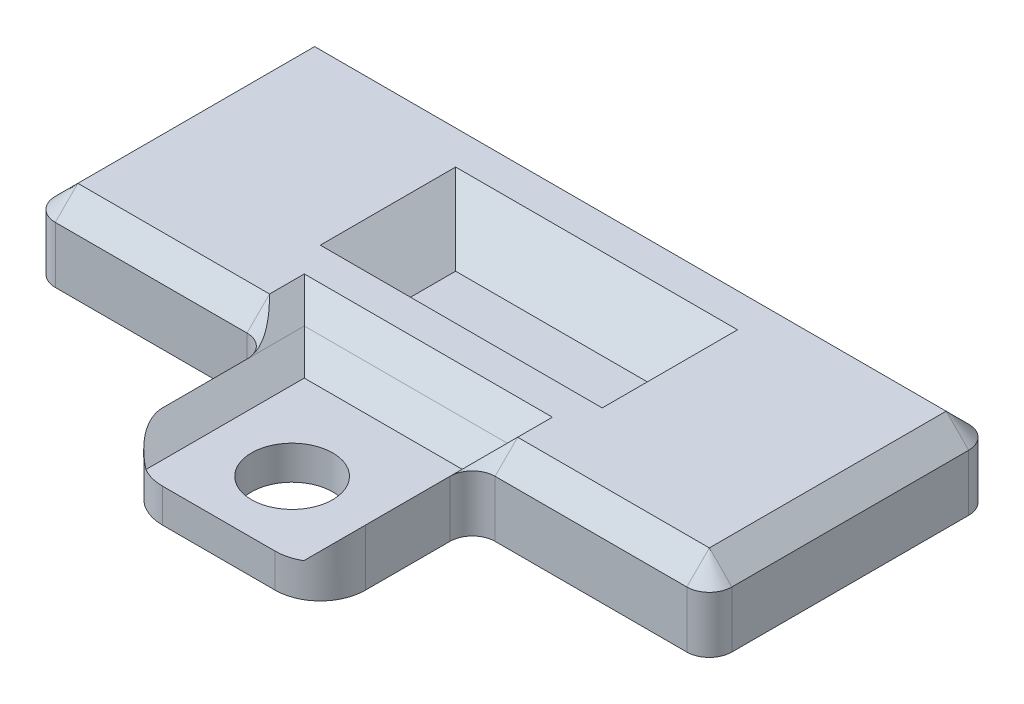
SolidWorks part; units mm, degrees
ref_plane "Front Plane" through (0, 0, 0) normal (0, 0, 1) x (1, 0, 0)
ref_plane "Top Plane" through (0, 0, 0) normal (0, 1, 0) x (1, 0, 0)
ref_plane "Right Plane" through (0, 0, 0) normal (1, 0, 0) x (0, 0, -1)
sketch "Sketch1" plane through (0, 0, 0) normal (0, 1, 0) x (1, 0, 0)
  line L0 (-4.5, -6.25) -> (-15, -6.25)
  line L1 (15, -6.25) -> (4.5, -6.25)
  line L2 (15, -6.25) -> (15, 6.25)
  line L3 (15, 6.25) -> (-15, 6.25)
  line L4 (-15, -6.25) -> (-15, 6.25)
  line L5 (15, -6.25) -> (-15, 6.25) construction
  line L6 (15, 6.25) -> (-15, -6.25) construction
  line L8 (-4.5, -6.25) -> (-4.5, -13)
  line L9 (-4.5, -13) -> (4.5, -13)
  line L10 (4.5, -6.25) -> (4.5, -13)
  line L11 (0, -6.25) -> (4.5, -13) construction
  line L12 (-4.5, -13) -> (0, -6.25) construction
  point P0 (0, 0)
  point P6 (0, -6.25)
  dimension "D1" = 30
  dimension "D2" = 12.5
  dimension "D3" = 6.75
  dimension "D4" = 9
  dimension "D5" = 10.5
extrude "Boss-Extrude1" add sketch "Sketch1" along normal blind 3.5
sketch "Sketch2" plane through (0, 0, 0) normal (0, -1, 0) x (1, 0, 0)
  line L0 (15, -6.25) -> (-15, -6.25) construction
  line L1 (-13, -5) -> (-9, -5)
  line L2 (-13, -5) -> (-13, 5)
  line L3 (-13, 5) -> (-9, 5)
  line L4 (-9, -5) -> (-9, 5)
  line L5 (-13, -5) -> (-9, 5) construction
  line L6 (-13, 5) -> (-9, -5) construction
  point P0 (-11, 0)
  dimension "D1" = 11
  dimension "D2" = 10
  dimension "D3" = 4
  dimension "D4" = 1.25
extrude "Cut-Extrude1" cut sketch "Sketch2" against normal blind 2.5
fillet "Fillet1" radius 1 6 edges at (15, 1.75, -6.25) (15, 1.75, 6.25) (4.5, 1.75, 6.25) (-4.5, 1.75, 6.25) (-15, 1.75, 6.25) (-15, 1.75, -6.25)
fillet "Fillet2" radius 1 4 edges at (-13, 1.25, 5) (-9, 1.25, 5) (-13, 1.25, -5) (-9, 1.25, -5)
mirror "Mirror1" about plane through (0, 0, 0) normal (1, 0, 0) of "Cut-Extrude1", "Fillet2"
sketch "Sketch3" plane through (0, 3.5, 0) normal (0, 1, 0) x (1, 0, 0)
  line L4 (-4.5, -13) -> (4.5, -13)
  line L5 (-4.5, -13) -> (-4.5, -4.7098)
  line L6 (-4.5, -4.7098) -> (4.5, -4.7098)
  line L7 (4.5, -13) -> (4.5, -4.7098)
  point P5 (-4.5, -7.25)
extrude "Cut-Extrude3" cut sketch "Sketch3" against normal blind 2
chamfer "Chamfer2" distance 1 angle 45 3 edges at (4.5, 1.5, 5.9799) (0, 1.5, 4.7098) (-4.5, 1.5, 5.9799)
chamfer "Chamfer3" distance 1 angle 45 14 edges at (-4.7929, 3.5, 6.5429) (-9.75, 3.5, 6.25) (-14.7071, 3.5, 5.9571) (-15, 3.5, 0) (-14.7071, 3.5, -5.9571) (0, 3.5, -6.25) (14.7071, 3.5, -5.9571) (15, 3.5, 0) (14.7071, 3.5, 5.9571) (9.75, 3.5, 6.25) (4.7929, 3.5, 6.5429) (4.5, 3.5, 5.9799) (0, 3.5, 4.7098) (-4.5, 3.5, 5.9799)
sketch "Sketch11" plane through (0, 1.5, 0) normal (0, 1, 0) x (1, 0, 0)
  line L0 (-14, 6.25) -> (14, 6.25) construction
  point P0 (0, -9.75)
  dimension "D1" = 16
hole_wizard "M3 Clearance Hole2" positions "Sketch11" profile "Sketch12" hole size "M3" standard "ANSI Metric" end condition through all
sketch "Sketch12" plane through (0, 1.5, 9.75) normal (1, 0, 0) x (0, 0, 1)
  line L0 (0, 0) -> (0, 1.5)
  line L1 (0, 1.5) -> (1.8, 1.5)
  line L2 (1.8, 1.5) -> (1.8, 0)
  line L5 (1.8, 0) -> (0, 0)
  line L11 (0, -6.35) -> (0, 107.95) construction
  dimension "Thru Hole Dia." = 3.6
  dimension "Thru Hole Depth" = 1.5
fillet "Fillet4" radius 2 2 edges at (4.5, 1.25, 13) (-4.5, 1.25, 13)
sketch "Sketch13" plane through (0, 3.5, 0) normal (0, 1, 0) x (1, 0, 0)
  line L0 (-14, 6.25) -> (14, 6.25) construction
  line L1 (6.25, -2.25) -> (-6.25, -2.25)
  line L2 (6.25, -2.25) -> (6.25, 3.75)
  line L3 (6.25, 3.75) -> (-6.25, 3.75)
  line L4 (-6.25, -2.25) -> (-6.25, 3.75)
  line L5 (6.25, -2.25) -> (-6.25, 3.75) construction
  line L6 (6.25, 3.75) -> (-6.25, -2.25) construction
  point P0 (0, 0.75)
  dimension "D1" = 12.5
  dimension "D2" = 6
  dimension "D3" = 5.5
extrude "Cut-Extrude4" cut sketch "Sketch13" against normal blind 2
chamfer "Chamfer4" distance 2 angle 45 4 edges at (0, 1.5, -3.75) (6.25, 1.5, -0.75) (0, 1.5, 2.25) (-6.25, 1.5, -0.75)
